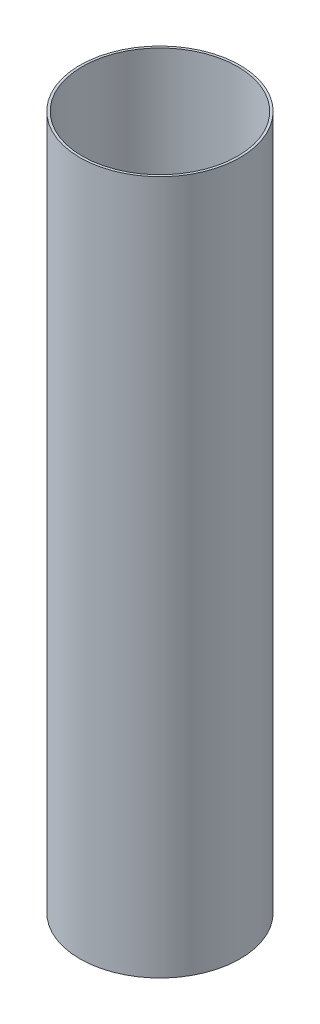
SolidWorks part; units mm, degrees
material "A-Glass Fiber"
ref_plane "Front Plane" through (0, 0, 0) normal (0, 0, 1) x (1, 0, 0)
ref_plane "Top Plane" through (0, 0, 0) normal (0, 1, 0) x (1, 0, 0)
ref_plane "Right Plane" through (0, 0, 0) normal (1, 0, 0) x (0, 0, -1)
sketch "Sketch1" plane through (0, 0, 0) normal (0, 1, 0) x (1, 0, 0)
  circle A0 centre (0, 0) radius 78.35
  circle A1 centre (0, 0) radius 80.75
  dimension "D1" = 156.7
  dimension "D2" = 2.4
extrude "Boss-Extrude1" add sketch "Sketch1" along normal blind 350 and the other way blind 350
